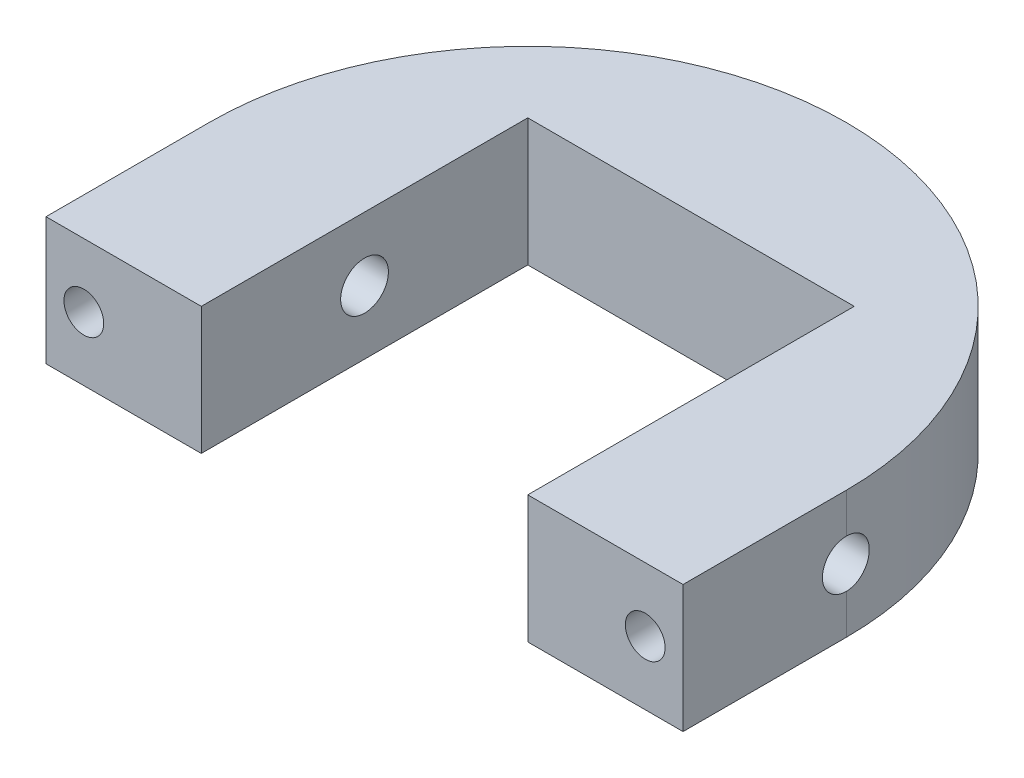
SolidWorks part; units mm, degrees
ref_plane "Front Plane" through (0, 0, 0) normal (0, 0, 1) x (1, 0, 0)
ref_plane "Top Plane" through (0, 0, 0) normal (0, 1, 0) x (1, 0, 0)
ref_plane "Right Plane" through (0, 0, 0) normal (1, 0, 0) x (0, 0, -1)
sketch "Sketch1" plane through (0, 0, 0) normal (0, 1, 0) x (1, 0, 0)
  circle A3 centre (0, 0) radius 40
extrude "Boss-Extrude1" add sketch "Sketch1" along normal blind 16
sketch "Sketch2" plane through (0, 16, 0) normal (0, 1, 0) x (1, 0, 0)
  line L1 (20.5, -20.5) -> (-20.5, -20.5)
  line L2 (20.5, -20.5) -> (20.5, 20.5)
  line L3 (20.5, 20.5) -> (-20.5, 20.5)
  line L4 (-20.5, -20.5) -> (-20.5, 20.5)
  point P4 (0, 0)
  dimension "D1" = 41
  dimension "D2" = 20.5
  dimension "D3" = 20.5
extrude "Cut-Extrude1" cut sketch "Sketch2" against normal through all
ref_plane "Plane1" through (0, 0, 0) normal (-1, 0, 0) x (0, 0, 1)
sketch "Sketch13" plane through (0, 0, 20.5) normal (0, 0, -1) x (-1, 0, 0)
  line L1 (-30.5, 31) -> (30.5, 31)
  line L2 (-30.5, 31) -> (-30.5, -15)
  line L3 (-30.5, -15) -> (30.5, -15)
  line L4 (30.5, 31) -> (30.5, -15)
  line L6 (20.5, 0) -> (20.5, 16) construction
  line L7 (-20.5, 0) -> (-20.5, 16) construction
  line L8 (20.5, 0) -> (-20.5, 0) construction
  line L9 (20.5, 16) -> (-20.5, 16) construction
  dimension "D1" = 10
  dimension "D2" = 10
  dimension "D3" = 15
  dimension "D4" = 15
extrude "Boss-Extrude4" add sketch "Sketch13" against normal blind 75
sketch "Sketch14" plane through (0, 31, 0) normal (0, 1, 0) x (1, 0, 0)
  line L0 (-30.5, -95.5) -> (30.5, -95.5) construction
  line L1 (24.5, -95.5) -> (-24.5, -95.5)
  line L2 (24.5, -95.5) -> (24.5, -28.5)
  line L3 (24.5, -28.5) -> (-24.5, -28.5)
  line L4 (-24.5, -95.5) -> (-24.5, -28.5)
  line L5 (30.5, -95.5) -> (30.5, -20.5) construction
  line L6 (-30.5, -95.5) -> (-30.5, -20.5) construction
  line L7 (-30.5, -20.5) -> (30.5, -20.5) construction
  dimension "D1" = 6
  dimension "D2" = 6
  dimension "D3" = 8
extrude "Cut-Extrude2" cut sketch "Sketch14" against normal blind 35
sketch "Sketch15" plane through (0, -4, 0) normal (0, 1, 0) x (1, 0, 0)
  line L0 (24.5, -95.5) -> (24.5, -28.5) construction
  line L1 (-24.5, -28.5) -> (24.5, -28.5)
  line L2 (-24.5, -28.5) -> (-24.5, -89.5)
  line L3 (-24.5, -89.5) -> (24.5, -89.5)
  line L4 (24.5, -28.5) -> (24.5, -89.5)
  line L5 (-24.5, -95.5) -> (24.5, -95.5) construction
  dimension "D1" = 6
extrude "Cut-Extrude3" cut sketch "Sketch15" against normal blind 5
fillet "Fillet1" radius 10 2 edges at (27.5, 31, 95.5) (-27.5, 31, 95.5)
fillet "Fillet2" radius 5 4 edges at (0, -9, 89.5) (0, -15, 95.5) (0, -15, 20.5) (0, -9, 28.5)
sketch "Sketch17" plane through (0, 16, 0) normal (0, 1, 0) x (1, 0, 0)
  circle A0 centre (0, 0) radius 41
  dimension "D1" = 82
extrude "Cut-Extrude5" cut sketch "Sketch17" along normal up to next
sketch "Sketch18" plane through (0, 16, 0) normal (0, 1, 0) x (1, 0, 0)
  line L0 (-20.5, 20.5) -> (-20.5, -20.5) construction
  line L1 (20.5, -20.5) -> (20.5, 20.5) construction
  line L2 (-20.5, -20.5) -> (20.5, -20.5) construction
  line L3 (-20.5, 20.5) -> (-20.5, -20.5) construction
  line L4 (20.5, -20.5) -> (20.5, 20.5) construction
  line L5 (-20.5, -20.5) -> (20.5, -20.5) construction
  line L6 (40, 0) -> (20.5, 0) construction
  line L8 (20.5, 0) -> (20.5, -20.5)
  line L9 (20.5, -20.5) -> (-20.5, -20.5)
  line L10 (-20.5, 0) -> (-20.5, -20.5)
  line L11 (40, 0) -> (20.5, 0)
  line L12 (40, 0) -> (40, -32.8748)
  line L13 (40, -32.8748) -> (24.5, -32.8748)
  line L14 (-40, 0) -> (-40, -32.8748)
  line L15 (24.5, -32.8748) -> (24.5, -28.5) construction
  line L16 (24.5, -28.5) -> (-24.5, -28.5) construction
  line L17 (-24.5, -28.5) -> (-24.5, -32.8748) construction
  line L18 (-24.5, -28.5) -> (-24.5, -32.8748)
  line L19 (24.5, -28.5) -> (-24.5, -28.5)
  line L20 (24.5, -32.8748) -> (24.5, -28.5)
  line L21 (-20.5, 0) -> (-40, 0)
  line L22 (-20.5, 0) -> (-40, 0) construction
  line L23 (-24.5, -32.8748) -> (-40, -32.8748)
  arc A0 (30.5, -25.8795) -> (-30.5, -25.8795) centre (0, 0) ccw construction
extrude "Boss-Extrude5" add sketch "Sketch18" against normal up to surface (16 mm away) up to face at (0, 0, 3.3599)
sketch "Sketch16" plane through (20.5, 0, 0) normal (-1, 0, 0) x (0, 0, 1)
  line L0 (20.5, 16) -> (-20.5, 16) construction
  line L2 (-20.5, 0) -> (-20.5, 16) construction
  circle A0 centre (0, 8) radius 3
  dimension "D1" = 6
  dimension "D2" = 8
  dimension "D3" = 20.5
extrude "Cut-Extrude4" cut sketch "Sketch16" against normal through all and the other way through all
sketch "Sketch19" plane through (0, 0, 32.8748) normal (0, 0, 1) x (1, 0, 0)
  line L0 (-40, 0) -> (-40, 16) construction
  line L1 (-40, 16) -> (-30.5, 16) construction
  line L2 (30.5, 16) -> (40, 16) construction
  line L3 (40, 0) -> (40, 16) construction
  point P0 (-35.25, 8)
  point P1 (35.25, 8)
  dimension "D1" = 4.75
  dimension "D2" = 8
  dimension "D3" = 8
  dimension "D4" = 4.75
hole_wizard "Ø5.0mm Dowel Hole1" positions "3DSketch1" profile "Sketch20" hole size "Ø5.0" standard "ANSI Metric"
sketch3d "3DSketch1"
  point P0 (-35.25, 8, 32.8748)
  point P3 (35.25, 8, 32.8748)
sketch "Sketch20" plane through (-35.25, 8, 32.8748) normal (1, 0, 0) x (0, -1, 0)
  line L0 (0, 0) -> (0, 26.5022)
  line L1 (0, 26.5022) -> (2.5, 25)
  line L2 (2.5, 25) -> (2.5, 0)
  line L5 (2.5, 0) -> (0, 0)
  line L10 (0, 26.5022) -> (-2.5, 25) construction
  line L11 (0, -6.35) -> (0, 107.95) construction
  dimension "Hole Dia." = 5
  dimension "Hole Depth" = 25
  dimension "Drill Angle" = 118
sketch "Sketch21" plane through (0, 16, 0) normal (0, 1, 0) x (1, 0, 0)
  line L0 (40, -32.8748) -> (40, 0) construction
  line L1 (-24.5, -95.5) -> (24.5, -95.5) construction
  line L2 (-40, 0) -> (-40, -32.8748) construction
  line L3 (20.5, -20.5) -> (20.5, 20.5) construction
  line L4 (40, -32.8748) -> (40, 0) construction
  line L5 (-24.5, -95.5) -> (24.5, -95.5) construction
  line L6 (-40, 0) -> (-40, -32.8748) construction
  line L7 (20.5, -20.5) -> (20.5, 20.5) construction
  line L8 (-20.5, -20.5) -> (20.5, -20.5) construction
  line L9 (40, -20.5) -> (-40, -20.5)
  line L10 (40, -20.5) -> (40, -95.5)
  line L11 (40, -95.5) -> (-40, -95.5)
  line L12 (-40, -20.5) -> (-40, -95.5)
extrude "Cut-Extrude6" cut sketch "Sketch21" against normal through all and the other way through all
